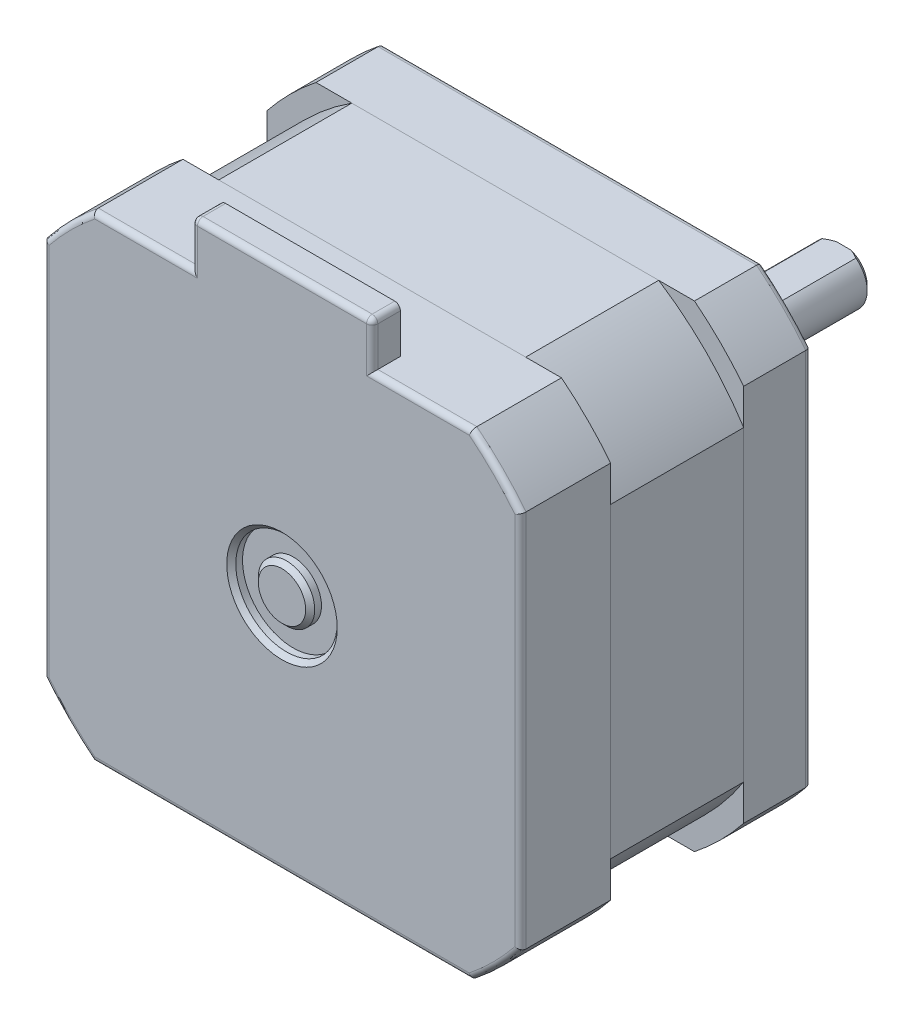
SolidWorks part; units mm, degrees
ref_plane "Plan de face" through (0, 0, 0) normal (0, 0, 1) x (1, 0, 0)
ref_plane "Plan de dessus" through (0, 0, 0) normal (0, 1, 0) x (1, 0, 0)
ref_plane "Plan de droite" through (0, 0, 0) normal (1, 0, 0) x (0, 0, -1)
sketch "Esquisse1" plane through (0, 0, 0) normal (0, 0, 1) x (1, 0, 0)
  line L0 (21.15, 16.7833) -> (21.15, -16.7833)
  line L1 (-21.15, 21.15) -> (21.15, 21.15) construction
  line L2 (-21.15, 21.15) -> (-21.15, -21.15) construction
  line L3 (-21.15, -21.15) -> (21.15, -21.15) construction
  line L4 (21.15, 21.15) -> (21.15, -21.15) construction
  line L5 (-21.15, 21.15) -> (21.15, -21.15) construction
  line L6 (-21.15, -21.15) -> (21.15, 21.15) construction
  line L7 (16.7833, -21.15) -> (-16.7833, -21.15)
  line L8 (-21.15, -16.7833) -> (-21.15, 16.7833)
  line L9 (-16.7833, 21.15) -> (16.7833, 21.15)
  arc A0 (-16.7833, 21.15) -> (-21.15, 16.7833) centre (0, 0) ccw
  arc A1 (21.15, 16.7833) -> (16.7833, 21.15) centre (0, 0) ccw
  arc A2 (-21.15, -16.7833) -> (-16.7833, -21.15) centre (0, 0) ccw
  arc A3 (16.7833, -21.15) -> (21.15, -16.7833) centre (0, 0) ccw
  point P0 (0, 0)
  dimension "D2" = 54
  dimension "D1" = 42.3
extrude "Boss.-Extru.1" add sketch "Esquisse1" along normal blind 6
sketch "Esquisse2" plane through (0, 0, 6) normal (0, 0, 1) x (1, 0, 0)
  line L23 (-13.6088, 21.15) -> (13.6088, 21.15)
  line L24 (16.7833, 21.15) -> (-16.7833, 21.15) construction
  line L25 (21.15, 13.6088) -> (21.15, -13.6088)
  line L26 (21.15, -16.7833) -> (21.15, 16.7833) construction
  line L27 (13.6088, -21.15) -> (-13.6088, -21.15)
  line L28 (-16.7833, -21.15) -> (16.7833, -21.15) construction
  line L29 (-21.15, -13.6088) -> (-21.15, 13.6088)
  line L30 (-21.15, 16.7833) -> (-21.15, -16.7833) construction
  arc A60 (-13.6088, 21.15) -> (-21.15, 13.6088) centre (0, 0) ccw
  arc A61 (21.15, 16.7833) -> (16.7833, 21.15) centre (0, 0) ccw construction
  arc A62 (21.15, 13.6088) -> (13.6088, 21.15) centre (0, 0) ccw
  arc A63 (13.6088, -21.15) -> (21.15, -13.6088) centre (0, 0) ccw
  arc A64 (-21.15, -13.6088) -> (-13.6088, -21.15) centre (0, 0) ccw
  dimension "D1" = 1.85
extrude "Boss.-Extru.2" add sketch "Esquisse2" along normal blind 11.8 separate body
sketch "Esquisse3" plane through (0, 0, 17.8) normal (0, 0, 1) x (1, 0, 0)
  line L0 (-16.7833, -21.15) -> (16.7833, -21.15) construction
  line L1 (21.15, -16.7833) -> (21.15, 16.7833) construction
  line L2 (16.7833, 21.15) -> (-16.7833, 21.15) construction
  line L3 (-21.15, 16.7833) -> (-21.15, -16.7833) construction
  line L4 (-16.7833, -21.15) -> (16.7833, -21.15)
  line L5 (21.15, -16.7833) -> (21.15, 16.7833)
  line L6 (16.7833, 21.15) -> (-16.7833, 21.15)
  line L7 (-21.15, 16.7833) -> (-21.15, -16.7833)
  arc A0 (-21.15, -16.7833) -> (-16.7833, -21.15) centre (0, 0) ccw construction
  arc A1 (16.7833, -21.15) -> (21.15, -16.7833) centre (0, 0) ccw construction
  arc A2 (21.15, 16.7833) -> (16.7833, 21.15) centre (0, 0) ccw construction
  arc A3 (-16.7833, 21.15) -> (-21.15, 16.7833) centre (0, 0) ccw construction
  arc A4 (-21.15, -16.7833) -> (-16.7833, -21.15) centre (0, 0) ccw
  arc A5 (16.7833, -21.15) -> (21.15, -16.7833) centre (0, 0) ccw
  arc A6 (21.15, 16.7833) -> (16.7833, 21.15) centre (0, 0) ccw
  arc A7 (-16.7833, 21.15) -> (-21.15, 16.7833) centre (0, 0) ccw
extrude "Boss.-Extru.3" add sketch "Esquisse3" along normal blind 8 separate body
sketch "Esquisse4" plane through (0, 21.15, 0) normal (0, 1, 0) x (1, 0, 0)
  line L0 (16.7833, -25.8) -> (-16.7833, -25.8) construction
  line L1 (8, -25.8) -> (-8, -25.8)
  line L2 (8, -25.8) -> (8, -23.3)
  line L3 (8, -23.3) -> (-8, -23.3)
  line L4 (-8, -25.8) -> (-8, -23.3)
  line L5 (0, 0) -> (0, -23.3) construction
  dimension "D1" = 2.5
  dimension "D2" = 16
extrude "Boss.-Extru.4" add sketch "Esquisse4" along normal blind 4
sketch "Esquisse5" plane through (0, 0, 0) normal (1, 0, 0) x (0, 0, -1)
  line L0 (0, 0) -> (-78.698, 0) construction
  line L2 (2, 11) -> (0, 11)
  line L3 (2, 11) -> (2, 4.5)
  line L4 (2, 4.5) -> (0, 4.5)
  line L5 (0, 11) -> (0, 4.5)
  line L6 (0, -16.7833) -> (0, 16.7833) construction
  line L7 (24, 0) -> (0, 0)
  line L8 (24, 0) -> (24, 2.5)
  line L9 (24, 2.5) -> (0, 2.5)
  line L10 (0, 0) -> (0, 2.5)
  dimension "D1" = 2
  dimension "D2" = 22
  dimension "D3" = 9
  dimension "D4" = 5
  dimension "D5" = 24
revolve "Révolution1" add sketch "Esquisse5" angle 360 about L0
fillet "Congé1" radius 0.5 14 edges at (-21.15, 0, 25.8) (-19.0919, 19.0919, 25.8) (-12.3916, 21.15, 25.8) (-8, 23.15, 25.8) (0, 25.15, 25.8) (8, 23.15, 25.8) (12.3916, 21.15, 25.8) (19.0919, 19.0919, 25.8) (21.15, 0, 25.8) (19.0919, -19.0919, 25.8) (0, -21.15, 25.8) (-19.0919, -19.0919, 25.8) (-8, 25.15, 24.55) (8, 25.15, 24.55)
fillet "Congé2" radius 0.5 8 edges at (-19.0919, 19.0919, 0) (-21.15, 0, 0) (-19.0919, -19.0919, 0) (0, -21.15, 0) (19.0919, -19.0919, 0) (21.15, 0, 0) (0, 21.15, 0) (19.0919, 19.0919, 0) tangent propagation no
chamfer "Chanfrein1" distance 0.4 angle 45 1 edges at (-2.5, 0, -24)
chamfer "Chanfrein2" distance 0.4 angle 45 2 edges at (-4.5, 0, -2) (-11, 0, -2)
sketch "Esquisse6" plane through (0, 0, 0) normal (1, 0, 0) x (0, 0, -1)
  line L0 (0, -2.5) -> (23.6, -2.5) construction
  line L1 (24, 2.5) -> (9, 2.5)
  line L2 (24, 2.5) -> (24, 2)
  line L3 (24, 2) -> (9, 2)
  line L4 (9, 2.5) -> (9, 2)
  line L5 (24, -2.1) -> (24, 2.1) construction
  line L6 (23.6, 2.5) -> (0, 2.5) construction
  dimension "D1" = 4.5
  dimension "D2" = 15
extrude "Enlèv. mat.-Extru.1" cut sketch "Esquisse6" against normal through all both and the other way through all
sketch "Esquisse7" plane through (0, 0, 25.8) normal (0, 0, 1) x (1, 0, 0)
  circle A0 centre (0, 0) radius 2.5
  circle A1 centre (0, 0) radius 4.5
  dimension "D1" = 5
  dimension "D2" = 9
extrude "Enlèv. mat.-Extru.2" cut sketch "Esquisse7" against normal blind 1
chamfer "Chanfrein3" distance 0.4 angle 45 2 edges at (4.5, 0, 25.8) (2.5, 0, 25.8)
hole_wizard "Trou taraudé M31" positions "Esquisse8" profile "Esquisse9" tap size "M3" standard "ISO"
sketch "Esquisse8" plane through (0, 0, 0) normal (0, 0, -1) x (-1, 0, 0)
  line L0 (-15.5, 15.5) -> (15.5, 15.5) construction
  line L1 (15.5, 15.5) -> (15.5, -15.5) construction
  line L2 (15.5, -15.5) -> (-15.5, -15.5) construction
  line L3 (-15.5, -15.5) -> (-15.5, 15.5) construction
  circle A0 centre (0, 0) radius 21.9203 construction
  point P5 (-15.5, 15.5)
  point P6 (15.5, 15.5)
  point P7 (15.5, -15.5)
  point P8 (-15.5, -15.5)
  dimension "D1" = 31
sketch "Esquisse9" plane through (15.5, -15.5, 0) normal (1, 0, 0) x (0, 1, 0)
  line L0 (0, 0) -> (0, 5.7511)
  line L1 (0, 5.7511) -> (1.25, 5)
  line L2 (1.25, 5) -> (1.25, 0)
  line L5 (1.25, 0) -> (0, 0)
  line L10 (0, 5.7511) -> (-1.25, 5) construction
  line L11 (0, -6.35) -> (0, 107.95) construction
  dimension "Diamètre du trou pour taraudage" = 2.5
  dimension "Profondeur du trou pour taraudage" = 5
  dimension "Angle de pointe" = 118
cosmetic thread "Filetage de perçage1" parameters "D1"=5, "D2"=3
cosmetic thread "Filetage de perçage2" parameters "D1"=5, "D2"=3
cosmetic thread "Filetage de perçage3" parameters "D1"=5, "D2"=3
cosmetic thread "Filetage de perçage4" parameters "D1"=5, "D2"=3
